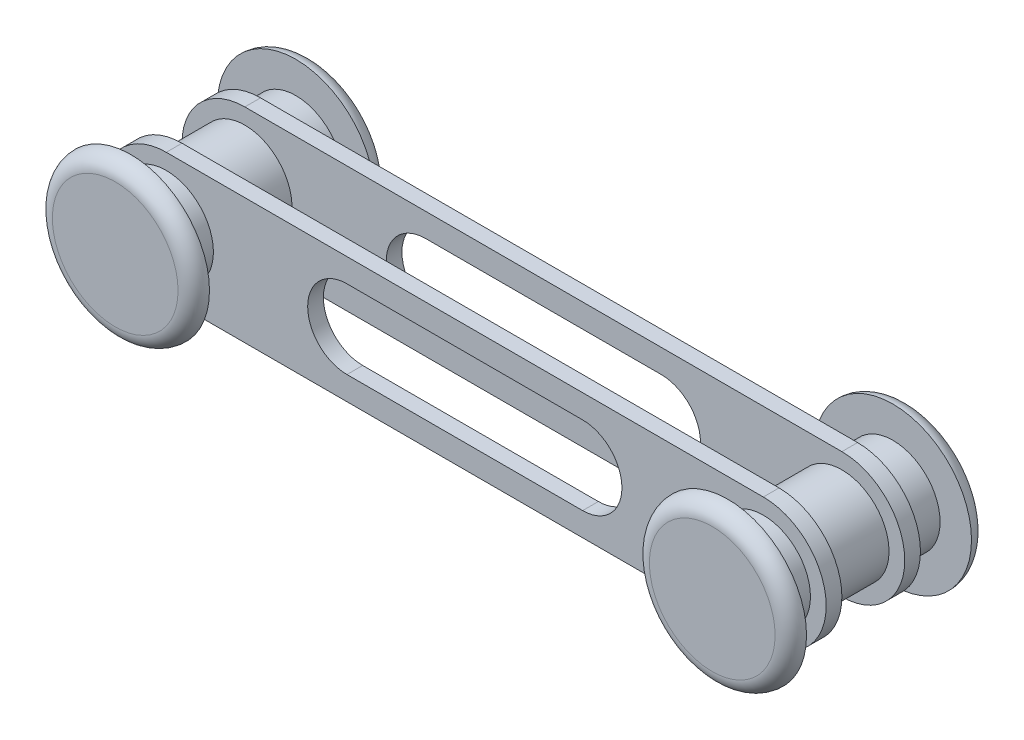
SolidWorks part; units mm, degrees
ref_plane "Front Plane" through (0, 0, 0) normal (0, 0, 1) x (1, 0, 0)
ref_plane "Top Plane" through (0, 0, 0) normal (0, 1, 0) x (1, 0, 0)
ref_plane "Right Plane" through (0, 0, 0) normal (1, 0, 0) x (0, 0, -1)
sketch "Sketch1" plane through (0, 0, 0) normal (0, 0, 1) x (1, 0, 0)
  circle A0 centre (0, 0) radius 30
  dimension "D1" = 60
extrude "Boss-Extrude1" add sketch "Sketch1" along normal mid plane 105
ref_plane "Plane1" through (0, 0, 30) normal (0, 0, 1) x (1, 0, 0)
sketch "Sketch2" plane through (0, 0, 30) normal (0, 0, 1) x (1, 0, 0)
  line L0 (0, 40) -> (0, -40) construction
  line L1 (0, 40) -> (380, 40)
  line L2 (0, 0) -> (380, 0) construction
  line L3 (380, 40) -> (380, -40) construction
  line L4 (0, -40) -> (380, -40)
  arc A0 (0, 40) -> (0, -40) centre (0, 0) ccw
  arc A1 (380, -40) -> (380, 40) centre (380, 0) ccw
  point P6 (0, 0)
  point P10 (380, 0)
  dimension "D1" = 40
  dimension "D2" = 380
extrude "Boss-Extrude2" add sketch "Sketch2" against normal blind 10
sketch "Sketch4" plane through (0, 0, 30) normal (0, 0, 1) x (1, 0, 0)
  line L0 (0, 0) -> (380, 0) construction
  line L1 (265, 0) -> (115, 0) construction
  line L2 (265, -25) -> (115, -25)
  line L3 (265, 25) -> (115, 25)
  arc A0 (265, -25) -> (265, 25) centre (265, 0) ccw
  arc A1 (115, 25) -> (115, -25) centre (115, 0) ccw
  point P6 (190, 0)
  dimension "D2" = 25
  dimension "D1" = 150
extrude "Cut-Extrude1" cut sketch "Sketch4" against normal up to next
sketch "Sketch5" plane through (0, 0, 0) normal (0, 0, 1) x (1, 0, 0)
  circle A0 centre (380, 0) radius 30
  dimension "D1" = 60
extrude "Boss-Extrude3" add sketch "Sketch5" along normal mid plane 105
mirror "Mirror1" about plane through (0, 0, 0) normal (0, 0, 1) of "Cut-Extrude1", "Boss-Extrude2"
sketch "Sketch6" plane through (0, 0, 52.5) normal (0, 0, 1) x (1, 0, 0)
  circle A0 centre (0, 0) radius 50
  circle A1 centre (380, 0) radius 50
  dimension "D1" = 100
extrude "Boss-Extrude4" add sketch "Sketch6" along normal blind 10
fillet "Fillet1" radius 10 2 edges at (430, 0, 62.5) (50, 0, 62.5)
mirror "Mirror2" about plane through (0, 0, 0) normal (0, 0, 1) of "Boss-Extrude4", "Fillet1"
